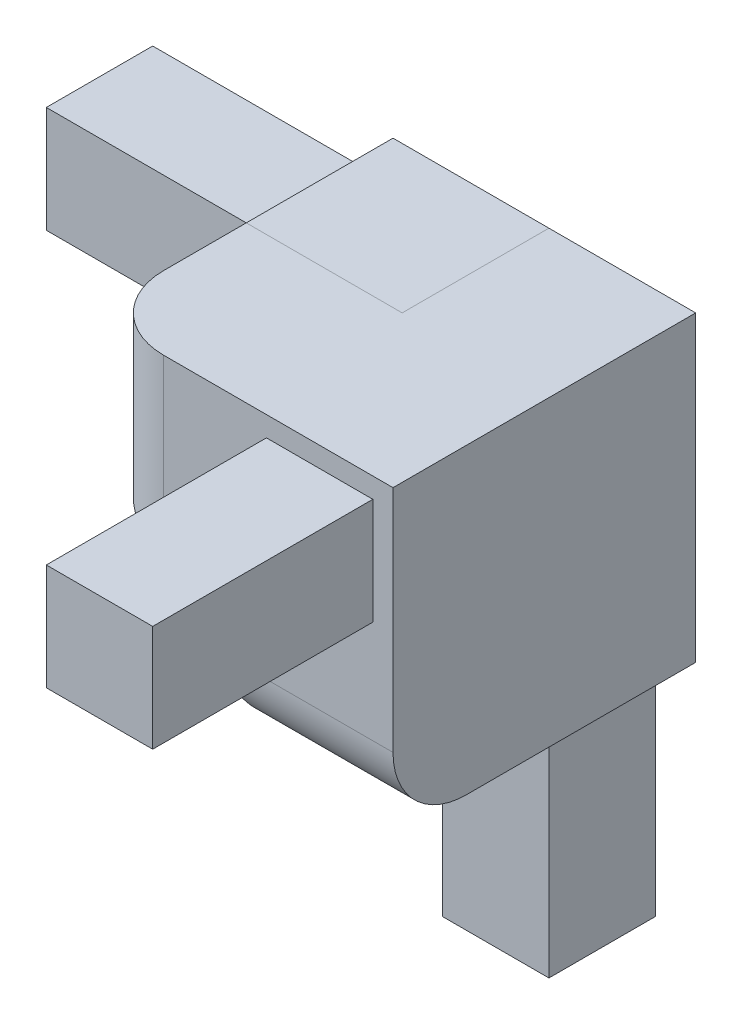
SolidWorks part; units mm, degrees
note: '?' marks a value the reader was unsure of.
material "6061 Alloy"
ref_plane "Front Plane" through (0, 0, 0) normal (0, 0, 1) x (1, 0, 0)
ref_plane "Top Plane" through (0, 0, 0) normal (0, 1, 0) x (1, 0, 0)
ref_plane "Right Plane" through (0, 0, 0) normal (1, 0, 0) x (0, 0, -1)
sketch "Sketch1" plane through (0, 35.0542, 0) normal (0, 1, 0) x (1, 0, 0.0003)
  line L23 (19.1557, 21.2) -> (24.9557, 21.2016)
  line L24 (24.9557, 21.2016) -> (24.9541, 27.0016)
  line L25 (24.9541, 27.0016) -> (19.1541, 27)
  line L26 (19.1541, 27) -> (19.1557, 21.2)
  line L27 (19.1557, 21.2) -> (24.9557, 21.2016)
  line L28 (24.9557, 21.2016) -> (24.9541, 27.0016)
  line L29 (24.9541, 27.0016) -> (19.1541, 27)
  line L30 (19.1541, 27) -> (19.1557, 21.2)
  dimension "D1" = 0.1
extrude "Boss-Extrude1" add sketch "Sketch1" against normal blind 12
sketch "Sketch2" plane through (9.5616, 0, 0) normal (1, 0, 0) x (0, 0, -1)
  line L14 (26.9948, 44.6542) -> (26.9948, 50.4542)
  line L15 (21.1948, 44.6542) -> (26.9948, 44.6542)
  line L16 (21.1948, 50.4542) -> (21.1948, 44.6542)
  line L17 (26.9948, 50.4542) -> (21.1948, 50.4542)
  line L18 (26.9948, 44.6542) -> (26.9948, 50.4542)
  line L19 (21.1948, 44.6542) -> (26.9948, 44.6542)
  line L20 (21.1948, 50.4542) -> (21.1948, 44.6542)
  line L21 (26.9948, 50.4542) -> (21.1948, 50.4542)
  dimension "D1" = 0.1
extrude "Boss-Extrude2" add sketch "Sketch2" against normal blind 12 separate body
sketch "Sketch3" plane through (0, 0, -11.5947) normal (0, 0, -1) x (-1, -0.0003, 0)
  line L8 (-24.9756, 50.4473) -> (-24.9739, 44.6473)
  line L9 (-24.9739, 44.6473) -> (-19.1739, 44.6489)
  line L10 (-19.1739, 44.6489) -> (-19.1756, 50.4489)
  line L11 (-19.1756, 50.4489) -> (-24.9756, 50.4473)
  line L12 (-24.9756, 50.4473) -> (-24.9739, 44.6473)
  line L13 (-24.9739, 44.6473) -> (-19.1739, 44.6489)
  line L14 (-19.1739, 44.6489) -> (-19.1756, 50.4489)
  line L15 (-19.1756, 50.4489) -> (-24.9756, 50.4473)
  dimension "D1" = 0.1
extrude "Boss-Extrude3" add sketch "Sketch3" against normal blind 12 separate body
sketch "Sketch4" plane through (0, 0, -11.5947) normal (0, 0, -1) x (-1, 0, 0)
  line L1 (-26.0616, 51.5542) -> (-18.0616, 51.5542)
  line L2 (-26.0616, 51.5542) -> (-26.0616, 43.5542)
  line L3 (-26.0616, 43.5542) -> (-18.0616, 43.5542)
  line L4 (-18.0616, 51.5542) -> (-18.0616, 43.5542)
extrude "Boss-Extrude4" add sketch "Sketch4" along normal up to surface (16.5 mm away)
sketch "Sketch5" plane through (9.5616, 0, 0) normal (1, 0, 0) x (0, 0, -1)
  line L0 (28.0948, 43.5542) -> (11.5948, 43.5542) construction
  line L1 (28.0948, 51.5542) -> (20.0948, 51.5542)
  line L2 (28.0948, 51.5542) -> (28.0948, 43.5542)
  line L3 (28.0948, 43.5542) -> (20.0948, 43.5542)
  line L4 (20.0948, 51.5542) -> (20.0948, 43.5542)
extrude "Boss-Extrude5" add sketch "Sketch5" along normal up to surface (16.5 mm away)
sketch "Sketch6" plane through (0, 35.0542, 0) normal (0, 1, 0) x (1, 0, 0)
  line L0 (26.0616, 20.0947) -> (26.0616, 28.0947) construction
  line L1 (26.0616, 28.0947) -> (18.0616, 28.0947)
  line L2 (26.0616, 28.0947) -> (26.0616, 20.0947)
  line L3 (26.0616, 20.0947) -> (18.0616, 20.0947)
  line L4 (18.0616, 28.0947) -> (18.0616, 20.0947)
  line L5 (26.0616, 28.0947) -> (18.0616, 28.0947) construction
  dimension "D1" = 8
extrude "Boss-Extrude6" add sketch "Sketch6" along normal up to surface (16.5 mm away)
ref_plane "Plane1" through (24.4035, 24.4035, -24.4035) normal (-0.5774, -0.5774, 0.5773) x (-0.8165, 0.4082, -0.4082)
sketch "Sketch8" plane through (0, 0, -11.5947) normal (0, 0, 1) x (1, 0, 0)
  line L0 (18.0616, 35.0542) -> (26.0616, 35.0542) construction
  line L1 (26.0616, 51.5542) -> (9.5616, 51.5542)
  line L2 (26.0616, 51.5542) -> (26.0616, 35.0542)
  line L3 (26.0616, 35.0542) -> (9.5616, 35.0542)
  line L4 (9.5616, 51.5542) -> (9.5616, 35.0542)
  line L5 (9.5616, 51.5542) -> (9.5616, 43.5542) construction
extrude "Boss-Extrude7" add sketch "Sketch8" against normal up to surface (16.5 mm away)
sketch "Sketch7" plane through (24.4035, 24.4035, -24.4035) normal (-0.5774, -0.5774, 0.5773) x (-0.8165, 0.4082, -0.4082)
  circle A0 centre (11.2374, -16.5883) radius 3.375
  dimension "D1" = 6.75
extrude "Cut-Extrude1" cut sketch "Sketch7" against normal blind 10 and the other way through all
fillet "Fillet2" radius 4
thread "Thread1" pitch 1.25 start angle 0, offset 0, length 20, pitch 1.25, diameter 6.75
ref_plane "Plane2" through (18.2461, 47.8722, -24.4127) normal (0, 0.7071, 0.7071) x (-0.8165, 0.4082, -0.4082)
sketch "Thread Profile1" plane through (18.2461, 47.8722, -24.4127) normal (0, 0.7071, 0.7071) x (-0.8165, 0.4082, -0.4082)
  line L0 (0, 0) -> (0, 1.25) construction
  line L1 (0, 0) -> (0.6766, 0.3906)
  line L2 (0.6766, 0.3906) -> (0.6766, 0.5469)
  line L3 (0.6766, 0.5469) -> (0, 0.9375)
  line L4 (0.6766, 0.4687) -> (0, 0.4687) construction
  line L11 (0, 0) -> (0, 0.9375)
  point P2 (0, 0)
  dimension "Pitch" = 1.25
  dimension "Profile_Angle" = 60
  dimension "Profile_Land" = 0.1562
  dimension "Profile_Height" = 0.6766
ref_plane "Plane3" through (35.2369, 35.2369, -35.2368) normal (-0.5774, -0.5774, 0.5773) x (-0.8165, 0.4082, -0.4082)
ref_plane "Plane4" through (22.1021, 22.1021, -22.1021) normal (-0.5774, -0.5774, 0.5773) x (-0.8165, 0.4082, -0.4082)
sketch "Sketch13" plane through (22.1021, 22.1021, -22.1021) normal (-0.5774, -0.5774, 0.5773) x (0.4082, 0.4082, 0.8165)
  circle A0 centre (8.7472, 18.026) radius 7.5
  dimension "D1" = 15
extrude "Cut-Extrude4" cut sketch "Sketch13" along normal up to next
ref_plane "Plane6" [suppressed] through (42.157, 42.157, -42.157) normal (-0.5774, -0.5774, 0.5773) x (-0.8165, 0.4082, -0.4082)
sketch "Sketch19" [suppressed] plane through (42.157, 42.157, -42.157) normal (-0.5774, -0.5774, 0.5773) x (-0.8165, 0.4082, -0.4082)
  line L1 (-16.2626, 10.9117) -> (38.7374, 10.9117)
  line L2 (-16.2626, 10.9117) -> (-16.2626, -44.0883)
  line L3 (-16.2626, -44.0883) -> (38.7374, -44.0883)
  line L4 (38.7374, 10.9117) -> (38.7374, -44.0883)
  point P4 (11.2374, 10.9117)
  point P6 (-16.2626, -16.5883)
  dimension "D1" = 55
extrude "Boss-Extrude12" [suppressed] add sketch "Sketch19" along normal up to vertex separate body
combine bodies "Combine5" [suppressed] operation type? subtract main body? 120 bodies to subtract? 111
sketch "Sketch22" [suppressed] plane through (9.5616, 0, 0) normal (1, 0, 0) x (0, 0, -1)
  line L12 (26.8947, 50.3542) -> (21.2947, 50.3542) construction
  line L13 (26.8947, 44.7542) -> (26.8947, 50.3542) construction
  line L14 (26.8947, 50.3542) -> (8.3671, 50.3542)
  line L15 (26.8947, 32.775) -> (26.8947, 50.3542)
  line L16 (8.3671, 50.3542) -> (26.8947, 32.775)
extrude "Cut-Extrude5" [suppressed] cut sketch "Sketch22" against normal through all
sketch "Sketch23" [suppressed] plane through (0, 35.0542, 0) normal (0, 1, 0) x (1, 0, 0)
  line L1 (24.8616, 21.2947) -> (24.8616, 26.8947) construction
  line L3 (24.8616, 26.8947) -> (19.2616, 26.8947) construction
  line L5 (24.8616, 11.3105) -> (24.8616, 26.8947)
  line L7 (24.8616, 26.8947) -> (8.4459, 26.8947)
  line L8 (8.4459, 26.8947) -> (24.8616, 11.3105)
extrude "Cut-Extrude6" [suppressed] cut sketch "Sketch23" against normal through all
sketch "Sketch24" [suppressed] plane through (0, 0, -11.5947) normal (0, 0, -1) x (-1, 0, 0)
  line L0 (-19.2616, 50.3542) -> (-24.8616, 50.3542) construction
  line L3 (-24.8616, 50.3542) -> (-24.8616, 44.7542) construction
  line L4 (-6.1057, 50.3542) -> (-24.8616, 50.3542)
  line L7 (-24.8616, 50.3542) -> (-24.8616, 33.5003)
  line L8 (-6.1057, 50.3542) -> (-24.8616, 33.5003)
extrude "Cut-Extrude7" [suppressed] cut sketch "Sketch24" against normal through all
sketch "Sketch25" [suppressed] plane through (24.9369, 24.9369, -24.9368) normal (-0.5774, -0.5774, 0.5773) x (0.8165, -0.4082, 0.4082)
  line L0 (-11.0332, 4.921) -> (-4.5013, 4.921) construction
  line L1 (1.3775, 18.0733) -> (-4.5013, 28.2556) construction
  line L2 (-4.5013, 4.921) -> (1.3775, 15.1034) construction
  line L3 (1.3775, 15.1034) -> (1.3775, 18.0733) construction
  line L4 (-18.8308, 26.7706) -> (-21.4436, 22.2452) construction
  line L5 (-4.5013, 28.2556) -> (-16.2588, 28.2556) construction
  line L6 (-16.2588, 28.2556) -> (-18.8308, 26.7706) construction
  line L7 (-21.4436, 22.2452) -> (-24.7096, 16.5883) construction
  line L8 (-16.2588, 4.921) -> (-11.0332, 4.921) construction
  line L9 (-24.7096, 16.5883) -> (-18.8308, 6.406) construction
  line L10 (-18.8308, 6.406) -> (-16.2588, 4.921) construction
  line L11 (-11.0332, 4.921) -> (-4.5013, 4.921)
  line L12 (1.3775, 18.0733) -> (-4.5013, 28.2556)
  line L13 (-4.5013, 4.921) -> (1.3775, 15.1034)
  line L14 (1.3775, 15.1034) -> (1.3775, 18.0733)
  line L15 (-18.8308, 26.7706) -> (-21.4436, 22.2452)
  line L16 (-4.5013, 28.2556) -> (-16.2588, 28.2556)
  line L17 (-16.2588, 28.2556) -> (-18.8308, 26.7706)
  line L18 (-21.4436, 22.2452) -> (-24.7096, 16.5883)
  line L19 (-16.2588, 4.921) -> (-11.0332, 4.921)
  line L20 (-24.7096, 16.5883) -> (-18.8308, 6.406)
  line L21 (-18.8308, 6.406) -> (-16.2588, 4.921)
extrude "Cut-Extrude8" [suppressed] cut sketch "Sketch25" against normal up to next
equation "\"gap\"= 0.1"
equation "\"D1@Sketch2\"=\"gap\""
equation "\"D1@Sketch1\"=\"gap\""
equation "\"D1@Sketch3\"=\"gap\""
